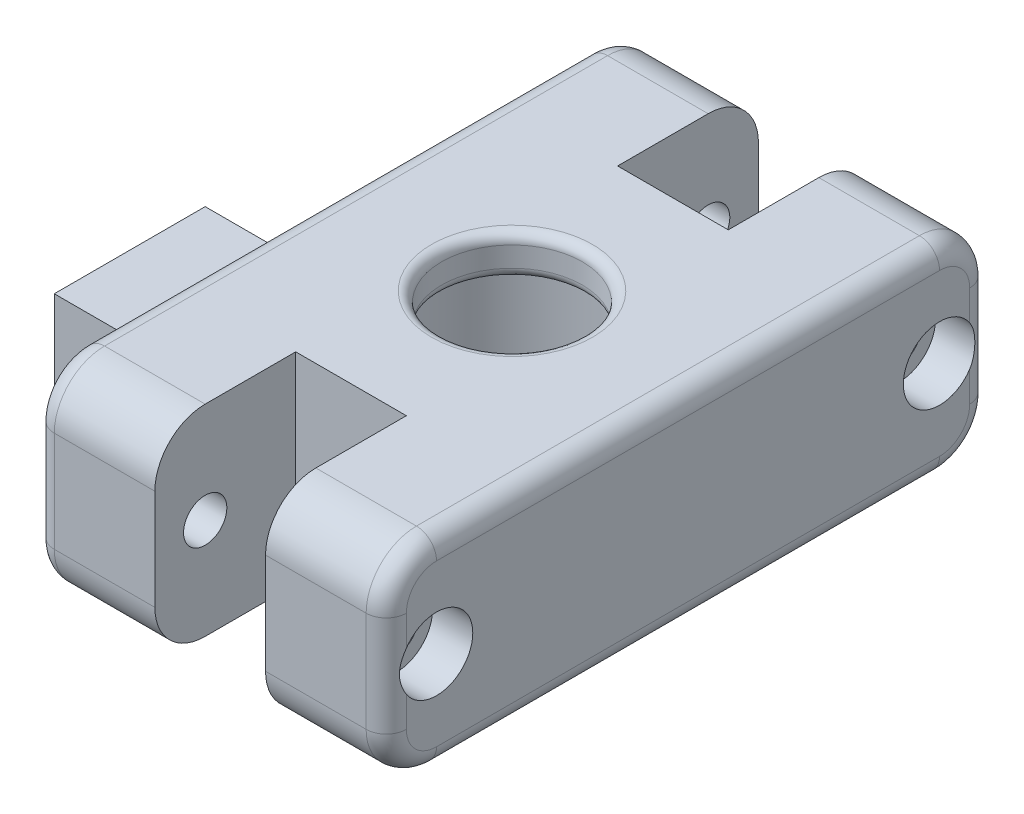
SolidWorks part; units mm, degrees
ref_plane "Front Plane" through (0, 0, 0) normal (0, 0, 1) x (1, 0, 0)
ref_plane "Top Plane" through (0, 0, 0) normal (0, 1, 0) x (1, 0, 0)
ref_plane "Right Plane" through (0, 0, 0) normal (1, 0, 0) x (0, 0, -1)
sketch "Sketch1" plane through (0, 0, 0) normal (0, 1, 0) x (1, 0, 0)
  line L1 (14.8917, -26.7815) -> (-20.1083, -26.7815)
  line L2 (14.8917, -26.7815) -> (14.8917, 33.2185)
  line L3 (14.8917, 33.2185) -> (-20.1083, 33.2185)
  line L4 (-20.1083, -26.7815) -> (-20.1083, 33.2185)
  dimension "D1" = 35
  dimension "D2" = 60
extrude "Boss-Extrude1" add sketch "Sketch1" along normal blind 20
sketch "Sketch2" plane through (0, 0, 0) normal (0, -1, 0) x (1, 0, 0)
  line L0 (-20.1083, 26.7815) -> (14.8917, 26.7815) construction
  line L1 (-20.1083, -33.2185) -> (-20.1083, 26.7815) construction
  circle A0 centre (-2.6083, -3.2185) radius 10
  dimension "D1" = 20
  dimension "D2" = 30
  dimension "D3" = 17.5
extrude "Cut-Extrude1" cut sketch "Sketch2" against normal blind 16
sketch "Sketch4" plane through (0, 16, 0) normal (0, -1, 0) x (1, 0, 0)
  line L0 (-20.1083, -33.2185) -> (-20.1083, 26.7815) construction
  line L2 (-20.1083, 26.7815) -> (14.8917, 26.7815) construction
  line L3 (14.8917, -33.2185) -> (-20.1083, -33.2185) construction
  circle A0 centre (-2.6083, -3.2185) radius 7
  dimension "D1" = 14
  dimension "D2" = 17.5
  dimension "D3" = 30
  dimension "D4" = 30
extrude "Cut-Extrude2" cut sketch "Sketch4" against normal through all
fillet "Fillet1" radius 2 8 edges at (-20.1083, 10, -33.2185) (-20.1083, 20, -3.2185) (-20.1083, 10, 26.7815) (-20.1083, 0, -3.2185) (14.8917, 10, 26.7815) (14.8917, 20, -3.2185) (14.8917, 10, -33.2185) (14.8917, 0, -3.2185)
sketch "Sketch5" plane through (0, 0, 0) normal (0, -1, 0) x (1, 0, 0)
  line L0 (-18.1083, 26.7815) -> (12.8917, 26.7815) construction
  line L1 (-8.1083, 26.7815) -> (2.8917, 26.7815)
  line L2 (-8.1083, 26.7815) -> (-8.1083, 12.7815)
  line L3 (-8.1083, 12.7815) -> (2.8917, 12.7815)
  line L4 (2.8917, 26.7815) -> (2.8917, 12.7815)
  line L5 (12.8917, -33.2185) -> (-18.1083, -33.2185) construction
  line L6 (2.8917, -33.2185) -> (-8.1083, -33.2185)
  line L7 (2.8917, -33.2185) -> (2.8917, -19.2185)
  line L8 (2.8917, -19.2185) -> (-8.1083, -19.2185)
  line L9 (-8.1083, -33.2185) -> (-8.1083, -19.2185)
  line L10 (-20.1083, -31.2185) -> (-20.1083, 24.7815) construction
  line L11 (14.8917, 24.7815) -> (14.8917, -31.2185) construction
  dimension "D1" = 11
  dimension "D2" = 11
  dimension "D3" = 12
  dimension "D4" = 12
  dimension "D5" = 12
  dimension "D6" = 14
  dimension "D7" = 14
extrude "Cut-Extrude3" cut sketch "Sketch5" against normal through all
sketch "Sketch6" plane through (-20.1083, 0, 0) normal (-1, 0, 0) x (0, 0, 1)
  line L0 (-33.2185, 20) -> (26.7815, 20) construction
  line L2 (-33.2185, 0) -> (-33.2185, 20) construction
  line L3 (26.7815, 20) -> (26.7815, 0) construction
  circle A0 centre (-28.2185, 10) radius 2.15
  circle A1 centre (21.7815, 10) radius 2.15
  dimension "D1" = 4.3
  dimension "D2" = 4.3
  dimension "D3" = 50
  dimension "D4" = 0
  dimension "D5" = 10
  dimension "D6" = 5
  dimension "D7" = 5
extrude "Cut-Extrude4" cut sketch "Sketch6" against normal through all
fillet "Fillet3" radius 5 8 edges at (-19.5225, 0.5858, 26.1957) (-19.5225, 19.4142, 26.1957) (14.3059, 19.4142, 26.1957) (14.3059, 0.5858, 26.1957) (7.8917, 0, 26.7815) (7.8917, 20, 26.7815) (-13.1083, 20, 26.7815) (-13.1083, 0, 26.7815)
fillet "Fillet4" radius 5 8 edges at (-19.5225, 0.5858, -32.6327) (14.3059, 0.5858, -32.6327) (14.3059, 19.4142, -32.6327) (-19.5225, 19.4142, -32.6327) (-13.1083, 20, -33.2185) (7.8917, 20, -33.2185) (7.8917, 0, -33.2185) (-13.1083, 0, -33.2185)
fillet "Fillet7" radius 1 2 edges at (-2.6083, 16, -10.2185) (-2.6083, 20, -10.2185)
sketch "Sketch7" plane through (-20.1083, 0, 0) normal (-1, 0, 0) x (0, 0, 1)
  line L0 (21.7815, 18) -> (-28.2185, 18) construction
  line L1 (2.7815, 18) -> (17.7815, 18)
  line L2 (2.7815, 18) -> (2.7815, 2)
  line L3 (2.7815, 2) -> (17.7815, 2)
  line L4 (17.7815, 18) -> (17.7815, 2)
  line L5 (-28.2185, 2) -> (21.7815, 2) construction
  line L6 (24.7815, 5) -> (24.7815, 15) construction
  dimension "D1" = 7
  dimension "D2" = 15
extrude "Boss-Extrude2" add sketch "Sketch7" along normal blind 7
sketch "Sketch8" plane through (-27.1083, 0, 0) normal (-1, 0, 0) x (0, 0, 1)
  line L0 (17.7815, 2) -> (17.7815, 18) construction
  line L1 (17.7815, 18) -> (2.7815, 18) construction
  circle A0 centre (13.7815, 14) radius 1.75
  dimension "D1" = 3.5
  dimension "D2" = 4
  dimension "D3" = 4
extrude "Cut-Extrude5" cut sketch "Sketch8" against normal blind 15
sketch "Sketch9" plane through (14.8917, 0, 0) normal (1, 0, 0) x (0, 0, -1)
  circle A0 centre (-21.7815, 10) radius 3.6
  circle A1 centre (28.2185, 10) radius 3.6
  dimension "D1" = 7.2
  dimension "D2" = 7.2
extrude "Cut-Extrude6" cut sketch "Sketch9" against normal blind 4
sketch "Sketch10" plane through (-20.1083, 0, 0) normal (-1, 0, 0) x (0, 0, 1)
  line L1 (23.7487, 6.4037) -> (25.8796, 9.9055)
  line L2 (25.8796, 9.9055) -> (23.9124, 13.5018)
  line L3 (23.9124, 13.5018) -> (19.8143, 13.5963)
  line L4 (19.8143, 13.5963) -> (17.6834, 10.0945)
  line L5 (17.6834, 10.0945) -> (19.6506, 6.4982)
  line L6 (19.6506, 6.4982) -> (23.7487, 6.4037)
  line L7 (-24.6479, 7.9865) -> (-24.6894, 12.0854)
  line L8 (-24.6894, 12.0854) -> (-28.26, 14.099)
  line L9 (-28.26, 14.099) -> (-31.7891, 12.0135)
  line L10 (-31.7891, 12.0135) -> (-31.7476, 7.9146)
  line L11 (-31.7476, 7.9146) -> (-28.177, 5.901)
  line L12 (-28.177, 5.901) -> (-24.6479, 7.9865)
  circle A0 centre (21.7815, 10) radius 3.55 construction
  circle A1 centre (-28.2185, 10) radius 3.55 construction
  dimension "D1" = 7.1
  dimension "D2" = 7.1
extrude "Cut-Extrude7" cut sketch "Sketch10" against normal blind 3
